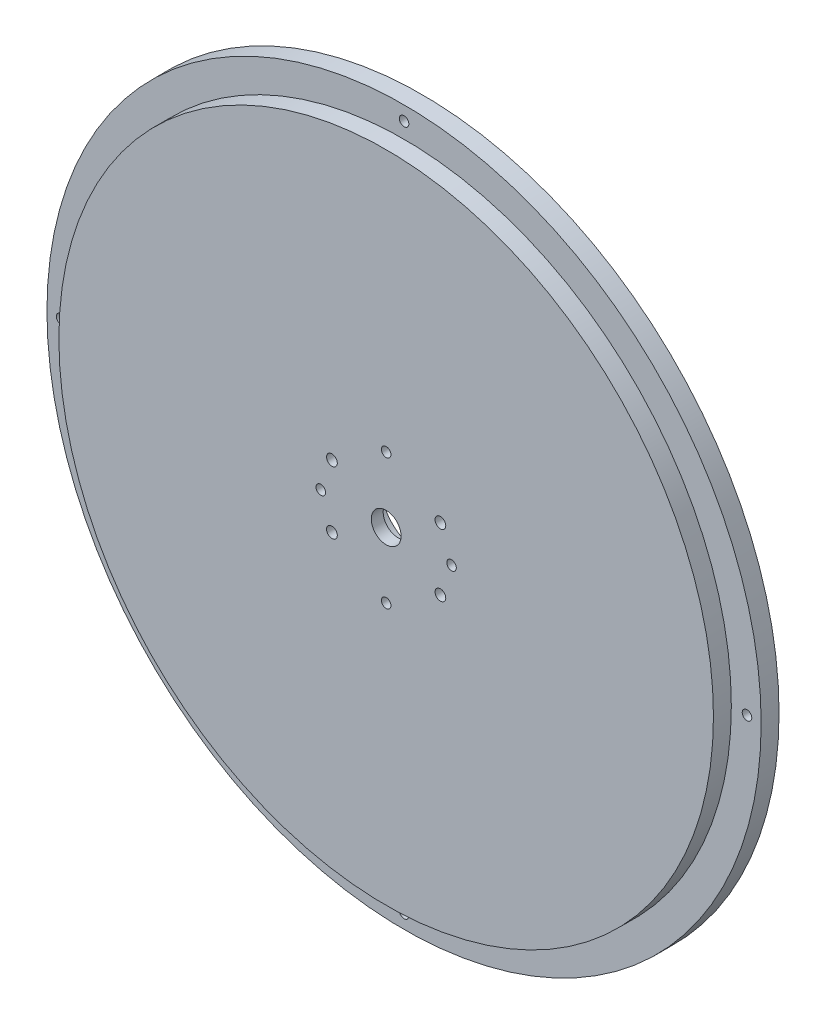
SolidWorks part; units mm, degrees
ref_plane "前视基准面" through (0, 0, 0) normal (0, 0, 1) x (1, 0, 0)
ref_plane "上视基准面" through (0, 0, 0) normal (0, 1, 0) x (1, 0, 0)
ref_plane "右视基准面" through (0, 0, 0) normal (1, 0, 0) x (0, 0, -1)
other "Configuration Table"
sketch "草图1" plane through (0, 0, 0) normal (0, 0, 1) x (1, 0, 0)
  circle A0 centre (0, 0) radius 119.75
  circle A1 centre (0, 0) radius 109.75
  dimension "D1" = 239.5
  dimension "D2" = 219.5
extrude "凸台-拉伸1" add sketch "草图1" along normal blind 12 contours A1
sketch "草图2" plane through (0, 0, 0) normal (0, 0, 1) x (1, 0, 0)
  circle A0 centre (0, 0) radius 119.75
  dimension "D1" = 239.5
extrude "凸台-拉伸2" add sketch "草图2" along normal blind 6 contours A0
sketch "草图3" plane through (0, 0, 0) normal (0, 0, 1) x (1, 0, 0)
  circle A0 centre (-115, 0) radius 1.6
  circle A1 centre (115, 0) radius 1.6
  circle A2 centre (0, -115) radius 1.6
  circle A3 centre (0, 115) radius 1.6
  dimension "D1" = 3.2
  dimension "D2" = 3.2
  dimension "D3" = 3.2
  dimension "D4" = 3.2
  dimension "D5" = 115
  dimension "D6" = 115
  dimension "D7" = 115
  dimension "D8" = 115
extrude "切除-拉伸1" cut sketch "草图3" along normal blind 10
sketch "草图4" plane through (0, 0, 0) normal (0, 0, -1) x (-1, 0, 0)
  line L0 (0, 0) -> (-21.9203, 0) construction
  line L1 (0, 0) -> (0, 21.9203) construction
  line L2 (0, 0) -> (21.9203, 0) construction
  line L3 (0, 0) -> (0, -21.9203) construction
  circle A0 centre (-21.9203, 0) radius 1.6
  circle A1 centre (0, 21.9203) radius 1.6
  circle A2 centre (21.9203, 0) radius 1.6
  circle A3 centre (0, -21.9203) radius 1.6
  dimension "D1" = 3.2
  dimension "D2" = 21.9203
  dimension "D4" = 90
  dimension "D5" = 21.9203
  dimension "D3" = 4
extrude "切除-拉伸2" cut sketch "草图4" against normal blind 20 contours A3
extrude "切除-拉伸3" cut sketch "草图4<5>" against normal blind 20
sketch "草图4<5>" plane through (0, 0, 0) normal (0, 0, -1) x (-1, 0, 0) same geometry as "草图4"
sketch "草图6" plane through (0, 0, 0) normal (0, 0, -1) x (-1, 0, 0)
  circle A0 centre (0, 0) radius 5
  dimension "D1" = 10
extrude "切除-拉伸5" cut sketch "草图6" against normal blind 20
sketch "草图7" plane through (0, 0, 0) normal (0, 0, -1) x (-1, 0, 0)
  line L0 (0, 0) -> (-18.1865, 10.5)
  line L1 (0, 0) -> (0, 115)
  line L2 (0, 0) -> (0, 21)
  line L3 (0, 0) -> (18.1865, 10.5)
  line L4 (0, 0) -> (18.1865, -10.5)
  line L5 (0, 0) -> (0, -21)
  line L6 (0, 0) -> (-18.1865, -10.5)
  circle A0 centre (-18.1865, 10.5) radius 1.8
  circle A5 centre (18.1865, 10.5) radius 1.8
  circle A6 centre (18.1865, -10.5) radius 1.8
  circle A8 centre (-18.1865, -10.5) radius 1.8
  circle A9 centre (0, 21) radius 1.8 [skipped]
  circle A10 centre (0, -21) radius 1.8 [skipped]
  point P15 (0, 0)
  point P20 (0, 0)
  dimension "D3" = 3.6
  dimension "D1" = 60
  dimension "D2" = 21
  dimension "D4" = 6
extrude "切除-拉伸8" cut sketch "草图7" against normal blind 30 contours A0 | A5 | A6 | A8
sketch "草图10" plane through (0, 0, 0) normal (0, 0, -1) x (-1, 0, 0)
  circle A0 centre (0, 0) radius 14
  dimension "D1" = 28
extrude "切除-拉伸9" cut sketch "草图10" against normal blind 8 contours A0
